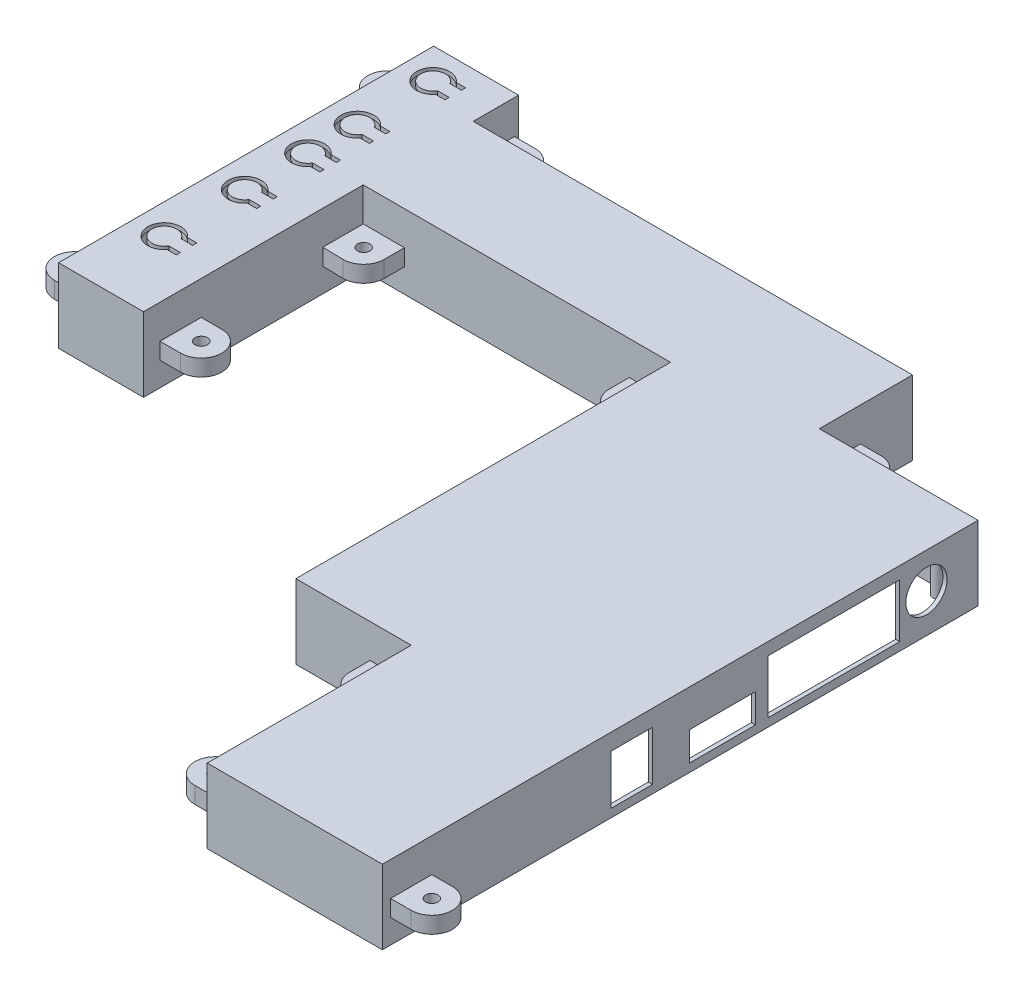
SolidWorks part; units mm, degrees
ref_plane "Front Plane" through (0, 0, 0) normal (0, 0, 1) x (1, 0, 0)
ref_plane "Top Plane" through (0, 0, 0) normal (0, 1, 0) x (1, 0, 0)
ref_plane "Right Plane" through (0, 0, 0) normal (1, 0, 0) x (0, 0, -1)
sketch "Sketch1" plane through (0, 0, 0) normal (0, 1, 0) x (1, 0, 0)
  line L5 (0, 0) -> (28, 0) construction
  line L17 (28, -51.5) -> (28, 0) construction
  line L19 (66.5, -51.5) -> (66.5, 91) construction
  line L20 (66.5, -51.5) -> (28, -51.5) construction
  line L25 (0, 0) -> (0, 91) construction
  line L26 (28, 91) -> (66.5, 91) construction
  line L36 (-78.5536, 113.6) -> (-78.5536, 124.6) construction
  line L37 (-95.1536, 37.6) -> (-78.5536, 37.6) construction
  line L38 (-95.1536, 37.6) -> (-95.1536, 124.6) construction
  line L39 (-95.1536, 124.6) -> (-78.5536, 124.6) construction
  line L40 (-78.5536, 37.6) -> (-78.5536, 91) construction
  line L41 (-78.5536, 113.6) -> (28, 113.6) construction
  line L43 (-78.5536, 91) -> (0, 91) construction
  line L48 (28, 91) -> (28, 113.6) construction
  circle A0 centre (-71.5536, 120.6) radius 7 construction
  circle A1 centre (-71.5536, 120.6) radius 5
  circle A2 centre (-71.5536, 120.6) radius 2.3
  circle A3 centre (-71.5536, 84) radius 7 construction
  circle A4 centre (-71.5536, 84) radius 5
  circle A5 centre (-71.5536, 84) radius 2.3
  circle A6 centre (-102.1536, 120.6) radius 7 construction
  circle A7 centre (-102.1536, 120.6) radius 5
  circle A8 centre (-102.1536, 120.6) radius 2.3
  circle A9 centre (-7, 84) radius 7 construction
  circle A10 centre (-7, 84) radius 5
  circle A11 centre (-7, 84) radius 2.3
  circle A12 centre (35, 98) radius 7 construction
  circle A13 centre (35, 98) radius 5
  circle A14 centre (35, 98) radius 2.3
  circle A15 centre (21, -7) radius 7 construction
  circle A16 centre (21, -7) radius 5
  circle A17 centre (21, -7) radius 2.3
  circle A18 centre (-71.5536, 44.6) radius 7 construction
  circle A19 centre (-71.5536, 44.6) radius 5
  circle A20 centre (-71.5536, 44.6) radius 2.3
  circle A21 centre (-102.1536, 44.6) radius 7 construction
  circle A22 centre (-102.1536, 44.6) radius 5
  circle A23 centre (-102.1536, 44.6) radius 2.3
  circle A24 centre (73.5, 84) radius 7 construction
  circle A25 centre (73.5, 84) radius 5
  circle A26 centre (73.5, 84) radius 2.3
  circle A27 centre (73.5, -44.5) radius 7 construction
  circle A28 centre (73.5, -44.5) radius 5
  circle A29 centre (73.5, -44.5) radius 2.3
  circle A30 centre (21, -44.5) radius 7 construction
  circle A31 centre (21, -44.5) radius 5
  circle A32 centre (21, -44.5) radius 2.3
  point P0 (0, 0)
  point P3 (0, 0)
  point P5 (0, 0)
  point P6 (0, 0)
  point P7 (0, 0)
  point P8 (0, 0)
  point P9 (-102.1536, 120.6)
  point P14 (0, 0)
  point P16 (0, 0)
  point P20 (0, 0)
  point P22 (0, 0)
  point P26 (0, 0)
  point P27 (19.4404, 91)
  point P30 (9.896, 91)
  point P34 (73.5, 81.715)
  dimension "D8" = 14
  dimension "D14" = 10
  dimension "D15" = 4.6
  dimension "D16" = 14
  dimension "D17" = 10
  dimension "D18" = 4.6
  dimension "D19" = 14
  dimension "D20" = 10
  dimension "D21" = 4.6
  dimension "D22" = 14
  dimension "D23" = 10
  dimension "D24" = 4.6
  dimension "D25" = 14
  dimension "D26" = 10
  dimension "D27" = 4.6
  dimension "D28" = 14
  dimension "D29" = 10
  dimension "D30" = 4.6
  dimension "D31" = 14
  dimension "D32" = 10
  dimension "D33" = 4.6
  dimension "D34" = 14
  dimension "D35" = 10
  dimension "D36" = 4.6
  dimension "D37" = 14
  dimension "D38" = 10
  dimension "D39" = 4.6
  dimension "D40" = 14
  dimension "D41" = 10
  dimension "D42" = 4.6
  dimension "D43" = 14
  dimension "D44" = 10
  dimension "D45" = 4.6
  dimension "D3" = 66.5
  dimension "D4" = 91
  dimension "D5" = 106.5536
  dimension "D6" = 142.5
  dimension "D7" = 38.5
  dimension "D9" = 16.6
  dimension "D10" = 87
  dimension "D11" = 28
  dimension "D12" = 11
  dimension "D13" = 22.6
sketch "Sketch2" plane through (0, 0, 0) normal (0, 1, 0) x (1, 0, 0)
  line L0 (-97.1536, 35.6) -> (-97.1536, 126.6)
  line L1 (-97.1536, 126.6) -> (-76.5536, 126.6)
  line L2 (-76.5536, 126.6) -> (-76.5536, 115.6)
  line L3 (-76.5536, 115.6) -> (30, 115.6)
  line L4 (30, 115.6) -> (30, 93)
  line L5 (30, 93) -> (68.5, 93)
  line L6 (68.5, 93) -> (68.5, -51.5)
  line L7 (68.5, -51.5) -> (26, -51.5)
  line L8 (26, -51.5) -> (26, -2)
  line L9 (26, -2) -> (-2, -2)
  line L10 (-2, -2) -> (-2, 88.899)
  line L11 (-2, 88.899) -> (-76.5536, 88.899)
  line L12 (-76.5536, 88.899) -> (-76.5536, 35.6)
  line L13 (-76.5536, 35.6) -> (-97.1536, 35.6)
  line L14 (-102.1536, 49.6) -> (-97.1536, 49.6)
  line L15 (66.5, -51.5) -> (28, -51.5) construction
  line L16 (-95.1536, 124.6) -> (-78.5536, 124.6) construction
  line L17 (-95.1536, 37.6) -> (-78.5536, 37.6) construction
  line L18 (-96.1571, 36.6) -> (-96.1571, 125.6)
  line L19 (-96.1571, 125.6) -> (-77.5536, 125.6)
  line L20 (-77.5536, 125.6) -> (-77.5536, 114.6)
  line L21 (-77.5536, 114.6) -> (29, 114.6)
  line L22 (29, 114.6) -> (29, 92)
  line L23 (29, 92) -> (67.5, 92)
  line L24 (67.5, 92) -> (67.5, -50.5)
  line L25 (67.5, -50.5) -> (27, -50.5)
  line L26 (27, -50.5) -> (27, -1)
  line L27 (27, -1) -> (-1, -1)
  line L28 (-1, -1) -> (-1, 89.899)
  line L29 (-1, 89.899) -> (-77.5536, 89.899)
  line L30 (-77.5536, 89.899) -> (-77.5536, 36.6)
  line L31 (-77.5536, 36.6) -> (-96.1571, 36.6)
  line L32 (-102.1536, 39.6) -> (-97.1536, 39.6)
  line L33 (-71.5536, 49.6) -> (-76.5536, 49.6)
  line L34 (-71.5536, 39.6) -> (-76.5536, 39.6)
  line L35 (-66.5536, 84) -> (-66.5536, 88.899)
  line L36 (-71.5536, 79) -> (-76.5536, 79.101)
  line L37 (-102.1536, 115.6) -> (-97.1536, 115.6)
  line L38 (-102.1536, 125.6) -> (-97.1536, 125.6)
  line L39 (-71.5536, 125.6) -> (-76.5536, 125.6)
  line L40 (-66.5536, 120.6) -> (-66.5536, 115.6)
  line L41 (-12, 84) -> (-12, 88.899)
  line L42 (-7, 79) -> (-2, 79)
  line L43 (35, 103) -> (30, 103)
  line L44 (40, 98) -> (40, 93)
  line L45 (73.5, 89) -> (68.5, 89)
  line L46 (73.5, 79) -> (68.5, 79)
  line L47 (16, -7) -> (16, -2)
  line L48 (21, -12) -> (26, -12)
  line L49 (21, -39.5) -> (26, -39.5)
  line L50 (21, -49.5) -> (26, -49.5)
  line L51 (73.5, -39.5) -> (68.5, -39.5)
  line L52 (73.5, -49.5) -> (68.5, -49.5)
  circle A0 centre (-7, 84) radius 7 construction
  circle A1 centre (-71.5536, 84) radius 7 construction
  circle A2 centre (-71.5536, 44.6) radius 5 construction
  circle A3 centre (-102.1536, 44.6) radius 5 construction
  circle A4 centre (-71.5536, 120.6) radius 5 construction
  circle A5 centre (35, 98) radius 5 construction
  circle A6 centre (73.5, 84) radius 5 construction
  circle A7 centre (73.5, -44.5) radius 5 construction
  circle A8 centre (21, -44.5) radius 5 construction
  arc A9 (-102.1536, 49.6) -> (-102.1536, 39.6) centre (-102.1536, 44.6) ccw
  circle A10 centre (21, -7) radius 5 construction
  circle A11 centre (-7, 84) radius 5 construction
  circle A12 centre (-102.1536, 44.6) radius 1.5
  circle A14 centre (-71.5536, 44.6) radius 1.5
  arc A15 (-71.5536, 39.6) -> (-71.5536, 49.6) centre (-71.5536, 44.6) ccw
  circle A16 centre (-71.5536, 84) radius 1.5
  arc A17 (-71.7556, 79.0041) -> (-66.5536, 84) centre (-71.5536, 84) ccw
  circle A19 centre (-102.1536, 120.6) radius 1.5
  arc A20 (-102.1536, 125.6) -> (-102.1536, 115.6) centre (-102.1536, 120.6) ccw
  circle A21 centre (21, -44.5) radius 1.5
  circle A22 centre (-71.5536, 120.6) radius 1.5
  arc A23 (-66.5536, 120.6) -> (-71.5536, 125.6) centre (-71.5536, 120.6) ccw
  circle A24 centre (-7, 84) radius 1.5
  arc A25 (-12, 84) -> (-7, 79) centre (-7, 84) ccw
  circle A26 centre (35, 98) radius 1.5
  arc A27 (40, 98) -> (35, 103) centre (35, 98) ccw
  circle A28 centre (73.5, 84) radius 1.5
  arc A29 (73.5, 79) -> (73.5, 89) centre (73.5, 84) ccw
  circle A30 centre (21, -7) radius 1.5
  arc A31 (16, -7) -> (21, -12) centre (21, -7) ccw
  arc A32 (21, -39.5) -> (21, -49.5) centre (21, -44.5) ccw
  circle A34 centre (73.5, -44.5) radius 1.5
  arc A35 (73.5, -49.5) -> (73.5, -39.5) centre (73.5, -44.5) ccw
  point P73 (0, 0)
  point P91 (0, 0)
  point P94 (0, 0)
  point P144 (0, 0)
  dimension "D17" = 3
  dimension "D18" = 3
  dimension "D19" = 3
  dimension "D20" = 3
  dimension "D21" = 3
  dimension "D22" = 3
  dimension "D23" = 5
  dimension "D24" = 3
  dimension "D25" = 3
  dimension "D26" = 3
  dimension "D27" = 5
  dimension "D28" = 3
  dimension "D29" = 5
  dimension "D30" = 5
  dimension "D31" = 3
  dimension "D1" = 2
  dimension "D2" = 2
  dimension "D3" = 0.9965
  dimension "D4" = 1
  dimension "D5" = 1
  dimension "D6" = 1
  dimension "D7" = 1
  dimension "D8" = 1
  dimension "D9" = 1
  dimension "D10" = 1
  dimension "D11" = 1
  dimension "D12" = 1
  dimension "D13" = 1
  dimension "D14" = 1
  dimension "D15" = 1
  dimension "D16" = 1
extrude "Boss-Extrude5" add sketch "Sketch2" along normal blind 18 contours L13 L12 L11 L10 L9 L8 L7 L6 L5 L4 L3 L2 L1 L0 L30 L31 L18 L19 L20 L21 L22 L23 L24 L25 L26 L27 L28 L29 region at (-96.9104, 0, -37.6)
extrude "Boss-Extrude6" add sketch "Sketch2<4>" along normal blind 1 from offset 17 contours L31 L30 L29 L28 L27 L26 L25 L24 L23 L22 L21 L20 L19 L18 region at (7.7745, 0, -50.4686)
sketch "Sketch2<4>" plane through (0, 0, 0) normal (0, 1, 0) x (1, 0, 0) same geometry as "Sketch2"
extrude "Boss-Extrude7" add sketch "Sketch2<5>" along normal blind 4 from offset 5.8 contours L14 A9 L32 L0 A12 | L34 A15 L33 L12 A14 | L36 A17 L35 L11 L12 A16 | L41 A25 L42 L10 L11 A24 | L47 A31 L48 L8 L9 A30 | L49 A32 L50 L8 A21 | L52 A35 L51 L6 A34 | L44 A27 L43 L4 L5 A26 | L38 A20 L37 L0 A19 | L40 A23 L39 L2 L3 A22 region at (-99.6536, 0, -39.7414) region at (-76.4122, 0, -44.6) region at (-99.6536, 0, -115.7414) region at (-76.4129, 0, -84) region at (-74.0536, 0, -125.4586) region at (-7, 0, -88.7583) region at (32.5, 0, -102.8586) region at (21, 0, 2.1414) region at (25.8586, 0, 44.5) region at (71, 0, 39.6414)
sketch "Sketch2<5>" plane through (0, 0, 0) normal (0, 1, 0) x (1, 0, 0) same geometry as "Sketch2"
sketch "Sketch5" plane through (0, 18, 0) normal (0, 1, 0) x (1, 0, 0)
  line L0 (-97.1536, 35.6) -> (-97.1536, 126.6) construction
  line L1 (-95.1536, 37.6) -> (-78.5536, 37.6) construction
  line L2 (-95.1536, 37.6) -> (-95.1536, 124.6) construction
  line L3 (-95.1536, 124.6) -> (-78.5536, 124.6) construction
  line L4 (-78.5536, 37.6) -> (-78.5536, 124.6) construction
  line L5 (-97.1536, 126.6) -> (-76.5536, 126.6) construction
  line L6 (-76.5536, 88.899) -> (-76.5536, 35.6) construction
  line L7 (-76.5536, 35.6) -> (-97.1536, 35.6) construction
  line L8 (-89.9036, 147.778) -> (-89.9036, 23.2346) construction
  line L9 (-86.7811, 121.7) -> (-84.5147, 121.7)
  line L10 (-84.5147, 121.7) -> (-84.5147, 120.7)
  line L11 (-87.3055, 120.7) -> (-84.5147, 120.7)
  line L12 (-93.8541, 119.2) -> (-81.9397, 119.2) construction
  line L13 (-84.5147, 116.7) -> (-84.5147, 117.7)
  line L14 (-86.7811, 116.7) -> (-84.5147, 116.7)
  line L15 (-87.3055, 117.7) -> (-84.5147, 117.7)
  line L16 (-86.7811, 103.35) -> (-84.5147, 103.35)
  line L17 (-84.5147, 103.35) -> (-84.5147, 102.35)
  line L18 (-87.3055, 102.35) -> (-84.5147, 102.35)
  line L19 (-94.4607, 100.85) -> (-80.3141, 100.85) construction
  line L20 (-84.5147, 98.35) -> (-84.5147, 99.35)
  line L21 (-86.7811, 98.35) -> (-84.5147, 98.35)
  line L22 (-87.3055, 99.35) -> (-84.5147, 99.35)
  line L23 (-86.7811, 91.35) -> (-84.5147, 91.35)
  line L24 (-84.5147, 91.35) -> (-84.5147, 90.35)
  line L25 (-87.3055, 90.35) -> (-84.5147, 90.35)
  line L26 (-94.4607, 88.85) -> (-81.9397, 88.85) construction
  line L27 (-84.5147, 86.35) -> (-84.5147, 87.35)
  line L28 (-86.7811, 86.35) -> (-84.5147, 86.35)
  line L29 (-87.3055, 87.35) -> (-84.5147, 87.35)
  line L30 (-86.7811, 76) -> (-84.5147, 76)
  line L31 (-84.5147, 76) -> (-84.5147, 75)
  line L32 (-87.3055, 75) -> (-84.5147, 75)
  line L33 (-94.4607, 73.5) -> (-84.5147, 73.5) construction
  line L34 (-84.5147, 71) -> (-84.5147, 72)
  line L35 (-86.7811, 71) -> (-84.5147, 71)
  line L36 (-87.3055, 72) -> (-84.5147, 72)
  line L37 (-86.7811, 56.5) -> (-84.5147, 56.5)
  line L38 (-84.5147, 56.5) -> (-84.5147, 55.5)
  line L39 (-87.3055, 55.5) -> (-84.5147, 55.5)
  line L40 (-89.9036, 54) -> (-94.4607, 54) construction
  line L41 (-84.5147, 51.5) -> (-84.5147, 52.5)
  line L42 (-86.7811, 51.5) -> (-84.5147, 51.5)
  line L43 (-87.3055, 52.5) -> (-84.5147, 52.5)
  circle A0 centre (-89.9036, 109.25) radius 3.5 construction
  circle A1 centre (-89.9036, 109.25) radius 2.25 construction
  circle A2 centre (-89.9036, 63) radius 2.25 construction
  circle A3 centre (-89.9036, 63) radius 3.5 construction
  arc A4 (-87.3055, 120.7) -> (-87.3055, 117.7) centre (-89.9036, 119.2) ccw
  arc A6 (-86.7811, 121.7) -> (-86.7811, 116.7) centre (-89.9036, 119.2) ccw
  arc A7 (-87.3055, 102.35) -> (-87.3055, 99.35) centre (-89.9036, 100.85) ccw
  arc A8 (-86.7811, 103.35) -> (-86.7811, 98.35) centre (-89.9036, 100.85) ccw
  arc A9 (-87.3055, 90.35) -> (-87.3055, 87.35) centre (-89.9036, 88.85) ccw
  arc A10 (-86.7811, 91.35) -> (-86.7811, 86.35) centre (-89.9036, 88.85) ccw
  arc A11 (-87.3055, 75) -> (-87.3055, 72) centre (-89.9036, 73.5) ccw
  arc A12 (-86.7811, 76) -> (-86.7811, 71) centre (-89.9036, 73.5) ccw
  arc A13 (-87.3055, 55.5) -> (-87.3055, 52.5) centre (-89.9036, 54) ccw
  arc A14 (-86.7811, 56.5) -> (-86.7811, 51.5) centre (-89.9036, 54) ccw
  point P20 (-86.6232, 117.8062)
  point P22 (-87.4734, 117.5552)
  point P33 (-81.9397, 118.3199)
  point P34 (0, 0)
  point P35 (0, 0)
  point P36 (-89.9036, 118.596)
  point P48 (-113.6206, 94.7705)
  point P49 (-89.9036, 102.2679)
  point P50 (-80.3141, 100.4279)
  point P51 (-94.4607, 99.9213)
  point P63 (-89.9036, 89.8367)
  point P75 (-89.9036, 78.8998)
  point P76 (-89.9036, 48.3391)
  point P87 (-123.6839, 51.3658)
  point P88 (-89.9036, 46.9638)
  point P89 (-94.4607, 46.5166)
  point P90 (-89.9036, 75.0529)
  point P91 (-89.9036, 86.9946)
  point P92 (-89.9036, 97.6876)
  point P93 (-84.5147, 73.5)
  point P94 (-94.4607, 73.5)
  point P95 (-81.9397, 88.85)
  point P96 (-94.4607, 88.85)
  point P97 (0, 0)
  dimension "D5" = 4.5
  dimension "D6" = 4.5
  dimension "D7" = 7
  dimension "D8" = 7
  dimension "D12" = 3
  dimension "D13" = 4
  dimension "D17" = 3
  dimension "D18" = 4
  dimension "D22" = 3
  dimension "D23" = 4
  dimension "D27" = 3
  dimension "D28" = 4
  dimension "D32" = 3
  dimension "D33" = 4
  dimension "D1" = 2
  dimension "D2" = 2
  dimension "D3" = 2
  dimension "D4" = 2
  dimension "D9" = 5.25
  dimension "D10" = 46.25
  dimension "D11" = 15.35
  dimension "D14" = 1
  dimension "D15" = 2.7909
  dimension "D16" = 3
  dimension "D19" = 1
  dimension "D20" = 2.7909
  dimension "D21" = 3
  dimension "D24" = 1
  dimension "D25" = 2.7909
  dimension "D26" = 3
  dimension "D29" = 1
  dimension "D30" = 2.7909
  dimension "D31" = 3
  dimension "D34" = 1
  dimension "D35" = 2.7909
  dimension "D36" = 3
  dimension "D37" = 5.4
  dimension "D38" = 12
  dimension "D39" = 8.4
  dimension "D40" = 15.35
  dimension "D41" = 9
sketch "Sketch6" plane through (0, 18, 0) normal (0, 1, 0) x (1, 0, 0)
  line L0 (-89.9036, 147.778) -> (-89.9036, 23.2346) construction
  line L2 (-95.1536, 37.6) -> (-78.5536, 37.6) construction
  line L3 (-95.1536, 37.6) -> (-95.1536, 124.6) construction
  line L4 (-95.1536, 124.6) -> (-78.5536, 124.6) construction
  line L5 (-78.5536, 37.6) -> (-78.5536, 124.6) construction
  circle A0 centre (-89.9036, 109.25) radius 2.25
  circle A1 centre (-89.9036, 109.25) radius 3.5
  circle A2 centre (-89.9036, 63) radius 2.25
  circle A3 centre (-89.9036, 63) radius 3.5
  dimension "D2" = 4.5
  dimension "D3" = 7
  dimension "D4" = 4.5
  dimension "D5" = 7
  dimension "D1" = 46.25
extrude "Cut-Extrude1" cut sketch "Sketch5" against normal through all both and the other way through all
extrude "Boss-Extrude9" add sketch "Sketch6" against normal blind 6 from surface starting at face at (-87.3691, 17, -119.2)
sketch "Sketch8" plane through (68.5, 0, 0) normal (1, 0, 0) x (0, 0, -1)
  line L0 (80.5, 4.4) -> (80.5, 14.4) construction
  line L1 (74, 2) -> (74, 15)
  line L2 (74, 2) -> (42, 2)
  line L3 (42, 2) -> (42, 15)
  line L4 (74, 15) -> (42, 15)
  line L5 (39, 2) -> (39, 9)
  line L6 (39, 2) -> (23, 2)
  line L7 (23, 2) -> (23, 9)
  line L8 (39, 9) -> (23, 9)
  line L9 (14, 2) -> (14, 14)
  line L10 (14, 2) -> (4, 2)
  line L11 (4, 2) -> (4, 14)
  line L12 (14, 14) -> (4, 14)
  line L13 (93, 18) -> (-51.5, 18) construction
  line L14 (0, 16.9334) -> (0, 1.0778) construction
  circle A0 centre (80.5, 9.4) radius 5
  dimension "D7" = 10
  dimension "D1" = 10
  dimension "D2" = 12
  dimension "D3" = 16
  dimension "D4" = 7
  dimension "D5" = 32
  dimension "D6" = 13
  dimension "D8" = 9
  dimension "D9" = 3
  dimension "D10" = 6.5
  dimension "D11" = 4
  dimension "D12" = 7.4
  dimension "D13" = 16
extrude "Cut-Extrude2" cut sketch "Sketch8" along direction (1, 0, 0) on the side against the normal blind 6 and the other way through all from surface starting at face at (68.5, 7.8, 44.5)
sketch "Sketch7" plane through (0, 17, 0) normal (0, -1, 0) x (1, 0, 0)
  line L0 (0, -45.5) -> (66.5, -45.5) construction
  line L1 (33.25, 0) -> (33.25, -91) construction
  line L3 (0, -91) -> (66.5, -91) construction
  line L4 (0, -91) -> (0, 0) construction
  line L5 (0, 0) -> (66.5, 0) construction
  line L6 (66.5, -91) -> (66.5, 0) construction
  line L7 (67.5, -92) -> (67.5, 50.5) construction
  line L9 (29, -92) -> (67.5, -92) construction
  circle A0 centre (1.2, -10.7) radius 1.2
  circle A1 centre (2, -89) radius 1.2
  circle A2 centre (63.3, -88.4) radius 1.2
  circle A3 centre (63, -1.6) radius 1.2
  circle A4 centre (52.0668, -32.9671) radius 3
  circle A5 centre (3, -52) radius 2
  point P18 (33.25, -45.5)
  point P25 (3.2432, -64.9355)
  dimension "D1" = 2.4
  dimension "D2" = 2.4
  dimension "D3" = 2.4
  dimension "D4" = 2.4
  dimension "D16" = 14.4332
  dimension "D17" = 6
  dimension "D18" = 32.9671
  dimension "D19" = 37
  dimension "D21" = 4
  dimension "D5" = 66.5
  dimension "D6" = 91
  dimension "D7" = 2
  dimension "D8" = 3.2
  dimension "D9" = 10.7
  dimension "D10" = 3.5
  dimension "D11" = 1.6
  dimension "D12" = 2
  dimension "D13" = 2.6
  dimension "D14" = 1
  dimension "D15" = 1
  dimension "D20" = 6
extrude "Boss-Extrude10" add sketch "Sketch7" along normal up to vertex (15 mm away) up to point (67.5, 2, -4)
